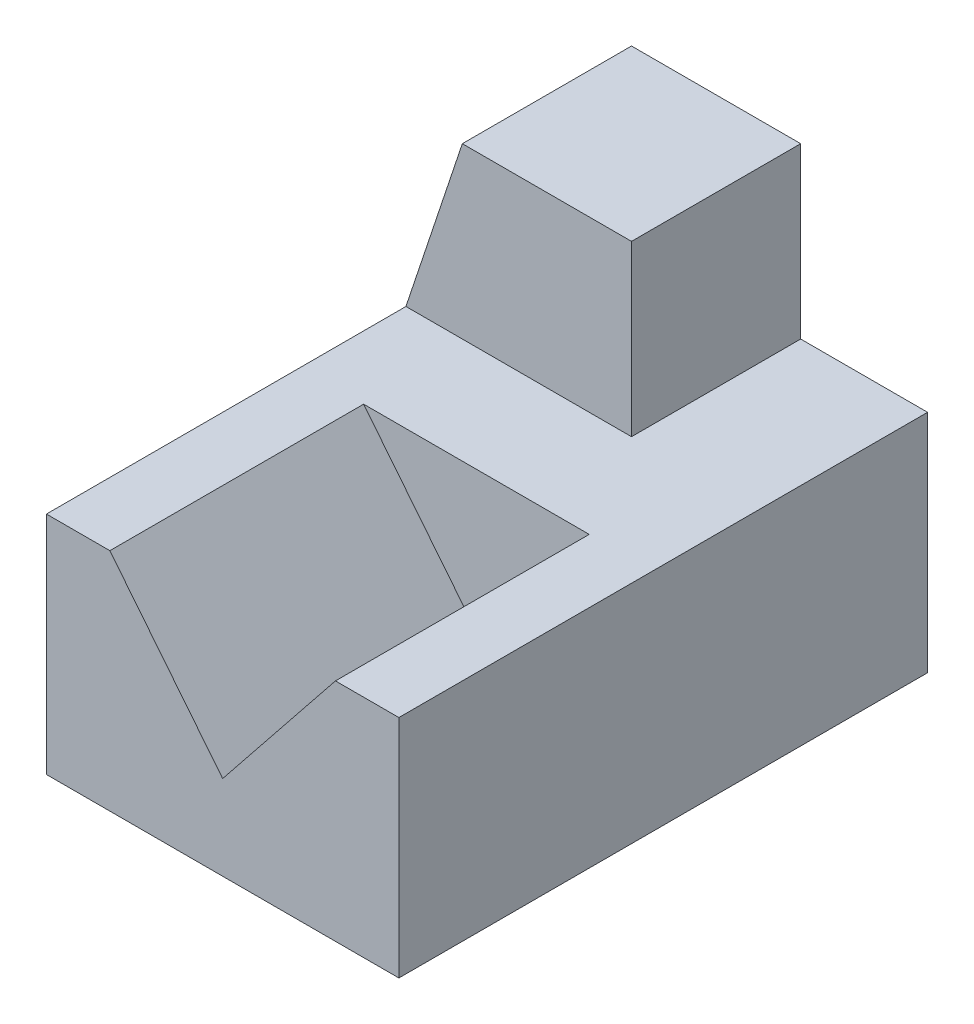
SolidWorks part; units mm, degrees
ref_plane "Front Plane" through (0, 0, 0) normal (0, 0, 1) x (1, 0, 0)
ref_plane "Top Plane" through (0, 0, 0) normal (0, 1, 0) x (1, 0, 0)
ref_plane "Right Plane" through (0, 0, 0) normal (1, 0, 0) x (0, 0, -1)
sketch "Sketch1" plane through (0, 0, 0) normal (0, 0, 1) x (1, 0, 0)
  line L0 (9, 32) -> (25, 12)
  line L1 (0, 0) -> (50, 0)
  line L2 (0, 0) -> (0, 32)
  line L3 (0, 32) -> (50, 32)
  line L4 (50, 0) -> (50, 32)
  line L5 (25, 12) -> (41, 32)
  line L6 (0, 32) -> (8, 56)
  line L7 (8, 56) -> (32, 56)
  line L8 (32, 56) -> (32, 32)
  dimension "D1" = 32
  dimension "D2" = 25
  dimension "D3" = 12
  dimension "D4" = 50
  dimension "D5" = 9
  dimension "D6" = 9
  dimension "D7" = 24
  dimension "D8" = 24
  dimension "D9" = 32
extrude "Boss-Extrude1" add sketch "Sketch1" along normal blind 75 contours L5 L0 L3 L2 L1 L4 | L0 L5 L3 region at (25, 25.3333, 0) region at (16.5365, 21.6292, 0)
extrude "Boss-Extrude2" add sketch "Sketch1<3>" along normal blind 24 contours L8 L7 L6 L3 region at (17.9048, 43.4286, 0)
sketch "Sketch1<3>" plane through (0, 0, 0) normal (0, 0, 1) x (1, 0, 0) same geometry as "Sketch1"
extrude "Cut-Extrude1" cut sketch "Sketch1<4>" against normal blind 36 from surface contours L0 L5 L3 region at (25, 25.3333, 0) starting at face at (25, 16, 75)
sketch "Sketch1<4>" plane through (0, 0, 0) normal (0, 0, 1) x (1, 0, 0) same geometry as "Sketch1"
